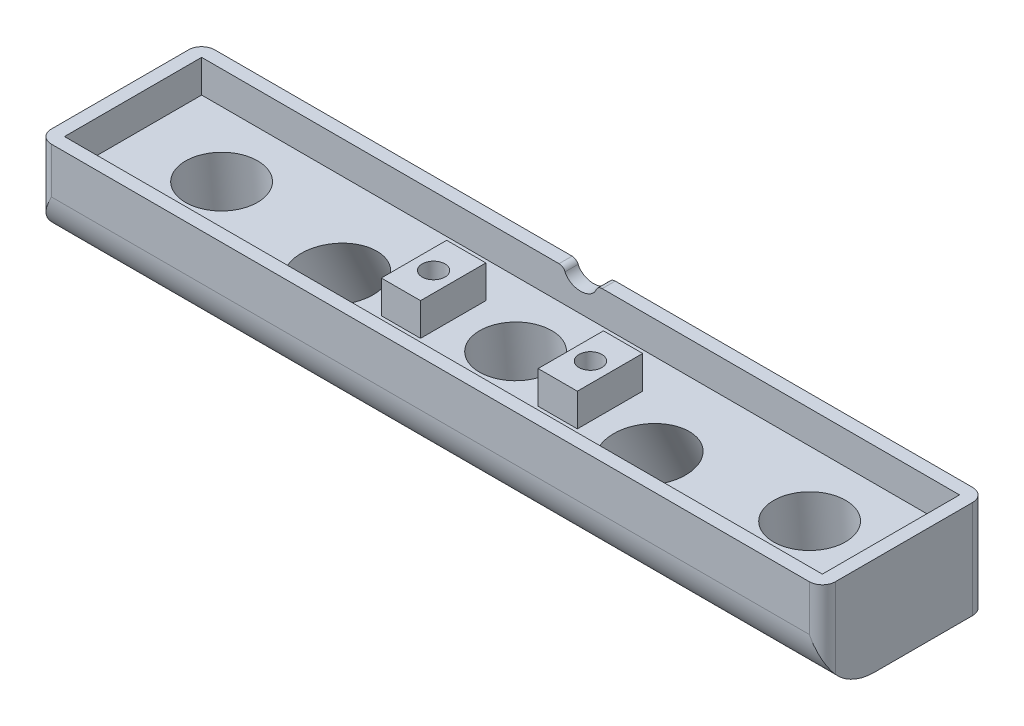
SolidWorks part; units mm, degrees
ref_plane "Front Plane" through (0, 0, 0) normal (0, 0, 1) x (1, 0, 0)
ref_plane "Top Plane" through (0, 0, 0) normal (0, 1, 0) x (1, 0, 0)
ref_plane "Right Plane" through (0, 0, 0) normal (1, 0, 0) x (0, 0, -1)
sketch "Base" plane through (0, 0, 0) normal (0, 1, 0) x (1, 0, 0)
  line L1 (60, -12.5) -> (-60, -12.5)
  line L2 (60, -12.5) -> (60, 12.5)
  line L3 (60, 12.5) -> (-60, 12.5)
  line L4 (-60, -12.5) -> (-60, 12.5)
  line L5 (60, -12.5) -> (-60, 12.5) construction
  line L6 (60, 12.5) -> (-60, -12.5) construction
  point P0 (0, 0)
  dimension "D1" = 25
  dimension "D2" = 120
extrude "Base EXT" add sketch "Base" along normal blind 10
ref_plane "3 LEDs - bottom" through (0, 11.0093, 0.9632) normal (0, 0.9962, 0.0872) x (1, 0, 0)
sketch "Sketch3" plane through (0, 11.0093, 0.9632) normal (0, 0.9962, 0.0872) x (1, 0, 0)
  line L0 (-60, 13.324) -> (-60, -11.5809) construction
  line L1 (60, -11.5809) -> (60, 13.324) construction
  line L2 (-45, 1.4191) -> (45, 1.4191) construction
  line L3 (0, 1.4191) -> (0, 20.1716) construction
  line L4 (-60, -11.5809) -> (60, -11.5809) construction
  circle A0 centre (-45, 1.4191) radius 5.5
  circle A1 centre (0, 1.4191) radius 5.5
  circle A2 centre (45, 1.4191) radius 5.5
  point P6 (-60, 0.8716)
  dimension "D1" = 11
  dimension "D2" = 15
  dimension "D3" = 15
  dimension "D4" = 13
extrude "LED bottom CUT" cut sketch "Sketch3" against normal through all
ref_plane "2 LED - top" through (0, 13.0017, 6.0628) normal (0, 0.9063, 0.4226) x (1, 0, 0)
sketch "LED for Top Row" plane through (0, 13.0017, 6.0628) normal (0, 0.9063, 0.4226) x (1, 0, 0)
  line L0 (-60, -7.1027) -> (60, -7.1027) construction
  line L1 (-46.4033, 9.1543) -> (-1.4033, 9.1543) construction
  line L2 (-23.9033, 9.1543) -> (-23.9033, 17.585) construction
  line L3 (0, -7.1027) -> (0, 20.7951) construction
  circle A0 centre (-23.9033, 1.6473) radius 5.5
  circle A1 centre (23.9033, 1.6473) radius 5.5
  dimension "D1" = 11
  dimension "D2" = 8.75
extrude "LED top CUT" cut sketch "LED for Top Row" against normal through all
sketch "Sketch5" plane through (0, 10, 0) normal (0, 1, 0) x (1, 0, 0)
  line L0 (-60, 12.5) -> (60, 12.5)
  line L1 (60, 12.5) -> (60, -12.5)
  line L2 (60, -12.5) -> (-60, -12.5)
  line L3 (-60, -12.5) -> (-60, 12.5)
  line L4 (-58, 10.5) -> (58, 10.5)
  line L5 (58, 10.5) -> (58, -10.5)
  line L6 (58, -10.5) -> (-58, -10.5)
  line L7 (-58, -10.5) -> (-58, 10.5)
  dimension "D1" = 2
  dimension "D2" = 2
  dimension "D3" = 2
  dimension "D5" = 2
extrude "Wire Box Rim" add sketch "Sketch5" along normal blind 5
sketch "Sketch6" plane through (0, 10, 0) normal (0, 1, 0) x (1, 0, 0)
  line L0 (-58, 0) -> (58, 0) construction
  line L1 (-15, 5) -> (-9, 5)
  line L2 (-15, 5) -> (-15, -5)
  line L3 (-15, -5) -> (-9, -5)
  line L4 (-9, 5) -> (-9, -5)
  line L5 (-58, 10.5) -> (-58, -10.5) construction
  line L6 (58, -10.5) -> (58, 10.5) construction
  line L7 (0, 0) -> (0, -5) construction
  line L8 (9, 5) -> (9, -5)
  line L9 (15, -5) -> (9, -5)
  line L10 (15, 5) -> (15, -5)
  line L11 (15, 5) -> (9, 5)
  line L12 (-12, 5) -> (-12, 1.7184) construction
  dimension "D1" = 6
  dimension "D2" = 10
  dimension "D3" = 5
  dimension "D4" = 12
extrude "Support Spacers" add sketch "Sketch6" along normal up to surface (5 mm away) up to face at (0, 15, 0)
sketch "Sketch8" plane through (0, 15, 0) normal (0, 1, 0) x (1, 0, 0)
  line L0 (12, -5) -> (12, 5) construction
  line L1 (15, -5) -> (9, -5) construction
  line L2 (9, 5) -> (15, 5) construction
  line L3 (12, 0) -> (13.7942, 0) construction
  line L6 (0, -10.5) -> (0, -3.6056) construction
  line L7 (-58, -10.5) -> (58, -10.5) construction
  circle A0 centre (12, 0) radius 1.75
  circle A1 centre (-12, 0) radius 1.75
  dimension "D1" = 3.5
extrude "M3 Screw CUT" cut sketch "Sketch8" against normal through all
sketch "M3 Nut" plane through (0, 0, 0) normal (0, -1, 0) x (1, 0, 0)
  line L0 (-12, 0) -> (-12, 5.4712) construction
  line L1 (-12, 3.1754) -> (-14.75, 1.5877)
  line L2 (-14.75, 1.5877) -> (-14.75, -1.5877)
  line L3 (-14.75, -1.5877) -> (-12, -3.1754)
  line L4 (-12, -3.1754) -> (-9.25, -1.5877)
  line L5 (-9.25, -1.5877) -> (-9.25, 1.5877)
  line L6 (-9.25, 1.5877) -> (-12, 3.1754)
  line L7 (0, 12.5) -> (0, 6.2927) construction
  line L8 (-60, 12.5) -> (60, 12.5) construction
  line L9 (9.25, 1.5877) -> (12, 3.1754)
  line L10 (9.25, -1.5877) -> (9.25, 1.5877)
  line L11 (12, -3.1754) -> (9.25, -1.5877)
  line L12 (14.75, -1.5877) -> (12, -3.1754)
  line L13 (14.75, 1.5877) -> (14.75, -1.5877)
  line L14 (12, 3.1754) -> (14.75, 1.5877)
  circle A0 centre (-12, 0) radius 2.75 construction
  circle A1 centre (12, 0) radius 2.75 construction
  dimension "D1" = 5.5
extrude "M3 Nut CUT" cut sketch "M3 Nut" against normal blind 3.5
sketch "Wire cut out" plane through (0, 0, -12.5) normal (0, 0, -1) x (-1, 0, 0)
  line L1 (-60, 15) -> (60, 15) construction
  ellipse E0 centre (0, 15) end of major axis (-2.5, 15) minor radius 2
  dimension "D1" = 2
  dimension "D2" = 5
extrude "Wire cut out CUT" cut sketch "Wire cut out" against normal up to surface (2 mm away) up to face at (0, 12.5, -10.5)
fillet "Fillet1" radius 1 3 edges at (0, 13, -12.5) (0, 13, -10.5) (2.5, 15, -11.5)
fillet "Fillet2" radius 1 1 edges at (-2.5, 15, -11.5) type face fillet first side face at (0.1336, 15, -3.8333) second side face at (-0.2277, 13.8571, -11.5)
fillet "Fillet3" radius 2 1 edges at (-60, 7.5, -12.5) type face fillet first side face at (-60, 7.5, 0) second side face at (0, 10.9575, -12.5)
fillet "Fillet4" radius 2 1 edges at (60, 7.5, -12.5) type face fillet first side face at (60, 7.5, 0) second side face at (0.5, 10.9575, -12.5)
fillet "Fillet5" radius 2 1 edges at (60, 7.5, 12.5) type face fillet first side face at (0, 7.5, 12.5) second side face at (60, 7.5, 1)
fillet "Fillet6" radius 2 1 edges at (-60, 7.5, 12.5) type face fillet first side face at (-60, 7.5, 1) second side face at (-1, 7.5, 12.5)
fillet "Fillet7" radius 8 3 edges at (59.4142, 0, 11.9142) (0, 0, 12.5) (-59.4142, 0, 11.9142)
equation "\"LED_DIA\"=11"
equation "\"D1@LED for Top Row\"=\"LED_DIA\""
equation "\"D1@Sketch3\"=\"LED_DIA\""
equation "\"WIRE_BOX_WALL\"=2"
equation "\"D1@Sketch5\"=\"WIRE_BOX_WALL\""
equation "\"D2@Sketch5\"=\"WIRE_BOX_WALL\""
equation "\"D3@Sketch5\"=\"WIRE_BOX_WALL\""
equation "\"D5@Sketch5\"=\"WIRE_BOX_WALL\""
